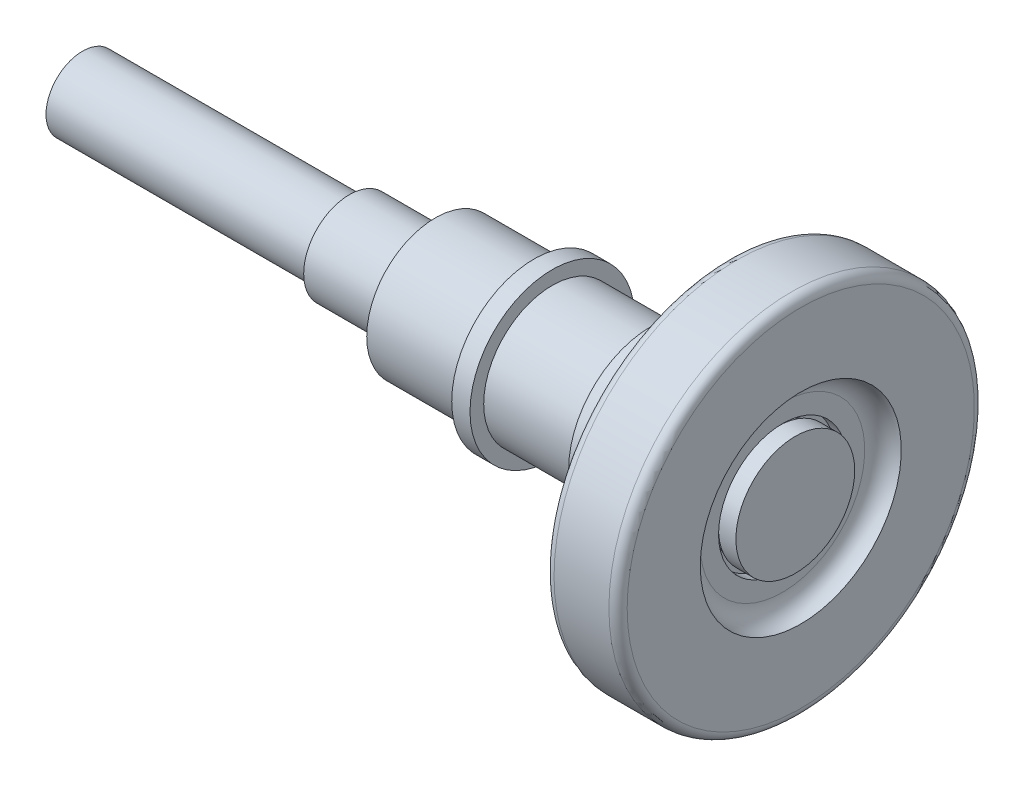
SolidWorks part; units mm, degrees
ref_plane "前视基准面" through (0, 0, 0) normal (0, 0, 1) x (1, 0, 0)
ref_plane "上视基准面" through (0, 0, 0) normal (0, 1, 0) x (1, 0, 0)
ref_plane "右视基准面" through (0, 0, 0) normal (1, 0, 0) x (0, 0, -1)
sketch "草图1" plane through (0, 0, 0) normal (0, 0, 1) x (1, 0, 0)
  line L0 (10, 100) -> (50, 100)
  line L1 (50, 100) -> (50, 55)
  line L2 (50, 55) -> (40, 55)
  line L3 (40, 55) -> (40, 35)
  line L6 (40, 35) -> (0, 35)
  line L7 (0, 35) -> (0, 70)
  line L8 (0, 70) -> (10, 70)
  line L9 (10, 70) -> (10, 100)
  line L10 (-1000, 0) -> (49000, 0) construction
  dimension "D1" = 35
  dimension "D2" = 70
  dimension "D3" = 10
  dimension "D4" = 40
  dimension "D5" = 100
  dimension "D6" = 55
  dimension "D7" = 10
revolve "旋转1" add sketch "草图1" angle 360 about L10
fillet "圆角1" radius 5 3 edges at (50, 0, 100) (10, 0, 100) (10, 0, 70)
fillet "圆角2" radius 10 1 edges at (40, 0, 55)
sketch "草图2" plane through (0, 0, 0) normal (-1, 0, 0) x (0, 0, 1)
  circle A0 centre (0, 0) radius 35
  circle A1 centre (0, 0) radius 35 construction
  circle A2 centre (0, 0) radius 45
  dimension "D1" = 90
extrude "凸台-拉伸1" add sketch "草图2" along normal blind 32 separate body
sketch "草图3" plane through (-32, 0, 0) normal (-1, 0, 0) x (0, 0, 1)
  circle A0 centre (0, 0) radius 35
  circle A1 centre (0, 0) radius 35 construction
extrude "凸台-拉伸2" add sketch "草图3" against normal blind 66
sketch "草图4" plane through (-32, 0, 0) normal (-1, 0, 0) x (0, 0, 1)
  circle A0 centre (0, 0) radius 37.5
  circle A1 centre (0, 0) radius 45 construction
  dimension "D1" = 75
extrude "凸台-拉伸3" add sketch "草图4" along normal blind 54
sketch "草图5" plane through (-86, 0, 0) normal (-1, 0, 0) x (0, 0, 1)
  circle A0 centre (0, 0) radius 45
  circle A1 centre (0, 0) radius 37.5 construction
  dimension "D1" = 90
extrude "凸台-拉伸4" add sketch "草图5" along normal blind 10
sketch "草图6" plane through (-96, 0, 0) normal (-1, 0, 0) x (0, 0, 1)
  circle A0 centre (0, 0) radius 37.5
  circle A1 centre (0, 0) radius 45 construction
  dimension "D1" = 75
extrude "凸台-拉伸5" add sketch "草图6" along normal blind 54
sketch "草图7" plane through (-150, 0, 0) normal (-1, 0, 0) x (0, 0, 1)
  circle A0 centre (0, 0) radius 25
  circle A1 centre (0, 0) radius 37.5 construction
  dimension "D1" = 50
extrude "凸台-拉伸6" add sketch "草图7" along normal blind 47
sketch "草图8" plane through (-197, 0, 0) normal (-1, 0, 0) x (0, 0, 1)
  circle A0 centre (0, 0) radius 20
  circle A1 centre (0, 0) radius 25 construction
  dimension "D1" = 40
extrude "凸台-拉伸7" add sketch "草图8" along normal blind 146
sketch "草图9" plane through (34, 0, 0) normal (1, 0, 0) x (0, 0, -1)
  circle A0 centre (0, 0) radius 31
  circle A1 centre (0, 0) radius 35 construction
  dimension "D1" = 62
extrude "凸台-拉伸8" add sketch "草图9" along normal blind 3.5
sketch "草图10" plane through (37.5, 0, 0) normal (1, 0, 0) x (0, 0, -1)
  circle A0 centre (0, 0) radius 32.5
  circle A1 centre (0, 0) radius 31 construction
  dimension "D1" = 65
extrude "凸台-拉伸9" add sketch "草图10" along normal blind 9.5
